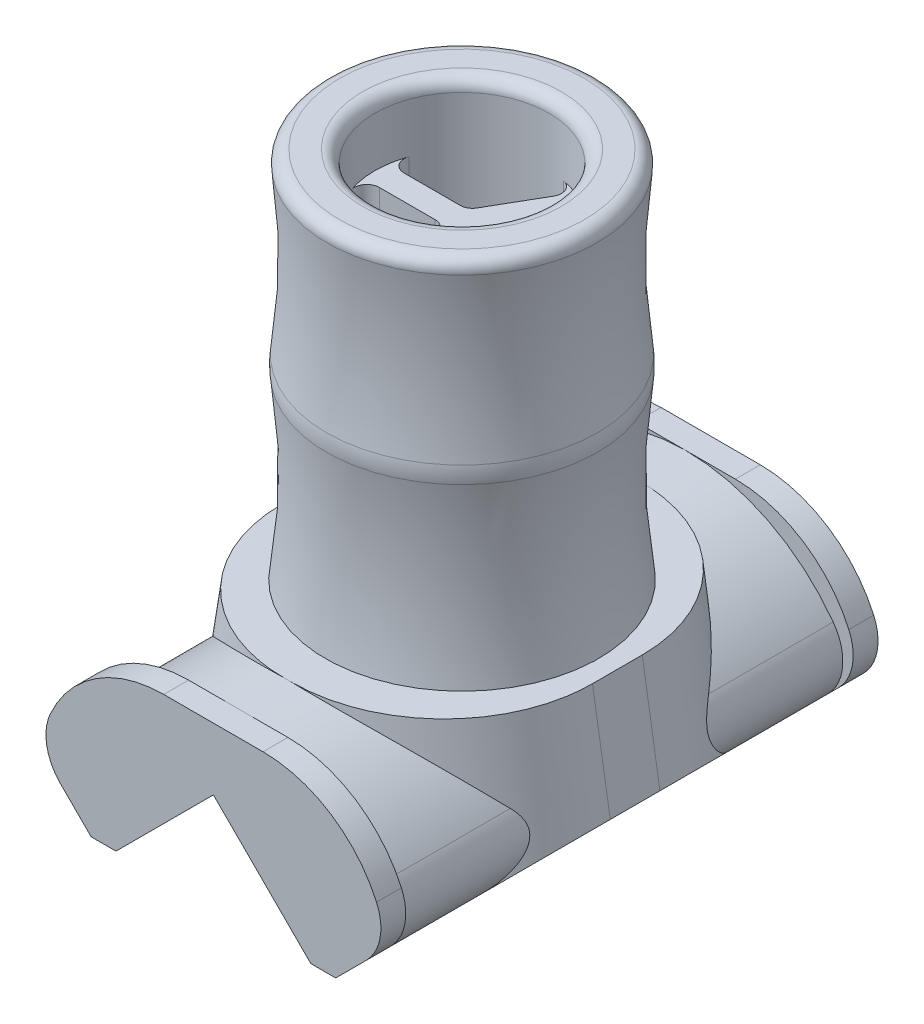
SolidWorks part; units mm, degrees
ref_plane "Front Plane" through (0, 0, 0) normal (0, 0, 1) x (1, 0, 0)
ref_plane "Top Plane" through (0, 0, 0) normal (0, 1, 0) x (1, 0, 0)
ref_plane "Right Plane" through (0, 0, 0) normal (1, 0, 0) x (0, 0, -1)
sketch "Sketch1" plane through (0, 0, 0) normal (0, 0, 1) x (1, 0, 0)
  line L0 (0, 0) -> (17.6777, 17.6777) construction
  line L1 (17.6777, 17.6777) -> (35.3553, 0) construction
  line L2 (35.3553, 0) -> (0, 0) construction
  line L3 (1.7766, 1.7766) -> (5.1777, 22.6777)
  line L4 (5.1777, 22.6777) -> (30.1777, 22.6777)
  line L5 (30.1777, 22.6777) -> (33.5787, 1.7766)
  line L6 (17.6777, 17.6777) -> (17.6777, 22.6777) construction
  line L7 (1.7766, 1.7766) -> (17.6777, 17.6777) construction
  line L8 (17.6777, 17.6777) -> (33.5787, 1.7766) construction
  line L9 (1.7766, 1.7766) -> (4.2951, 1.7766)
  line L10 (33.5787, 1.7766) -> (31.0603, 1.7766)
  line L11 (30.1221, 5.2333) -> (17.6777, 17.6777)
  line L12 (17.6777, 17.6777) -> (5.2333, 5.2333)
  line L13 (17.6777, 0) -> (-4.2005, 21.8781) construction
  line L14 (17.6777, 0) -> (36.9154, 19.2377) construction
  circle A0 centre (17.6777, 0) radius 12.5 construction
  circle A1 centre (17.6777, 0) radius 16 construction
  circle A2 centre (17.6777, 0) radius 13.5 construction
  arc A3 (4.2951, 1.7766) -> (5.2333, 5.2333) centre (17.6777, 0) cw
  arc A4 (31.0603, 1.7766) -> (30.1221, 5.2333) centre (17.6777, 0) ccw
  dimension "D3" = 25
  dimension "D4" = 32
  dimension "D6" = 27
  dimension "D7" = 25
  dimension "D1" = 90
  dimension "D2" = 45
  dimension "D5" = 5
  dimension "D8" = 45
extrude "Boss-Extrude1" add sketch "Sketch1" along normal blind 14 and the other way blind 14
sketch "Sketch2" plane through (0, 22.6777, 0) normal (0, 1, 0) x (1, 0, 0)
  line L0 (5.1777, 0) -> (30.1777, 0) construction
  line L1 (5.1777, 14) -> (5.1777, -14) construction
  line L2 (30.1777, 14) -> (30.1777, -14) construction
  circle A0 centre (17.6777, 0) radius 11
  dimension "D1" = 22
sketch "Sketch3" plane through (0, 0, 0) normal (0, 0, 1) x (1, 0, 0)
  line L0 (17.6777, 22.6777) -> (17.6777, 52.6777) construction
  line L1 (28.6777, 22.6777) -> (6.6777, 22.6777) construction
  line L2 (6.6777, 22.6777) -> (6.6777, 52.6777) construction
  line L3 (6.6777, 52.6777) -> (10.6777, 52.6777)
  line L4 (10.6777, 52.6777) -> (10.6777, 22.6777)
  line L5 (10.6777, 22.6777) -> (6.6777, 22.6777)
  line L7 (5.1777, 22.6777) -> (30.1777, 22.6777) construction
  arc A0 (6.6777, 37.6777) -> (6.6777, 22.6777) centre (-42.7566, 30.1777) cw
  arc A1 (6.6777, 37.6777) -> (6.6777, 52.6777) centre (-42.7566, 45.1777) ccw
  dimension "D3" = 15
  dimension "D4" = 50
  dimension "D5" = 50
  dimension "D1" = 30
  dimension "D2" = 4
revolve "Revolve1" add sketch "Sketch3" angle 360 about L0
fillet "Fillet1" radius 1 2 edges at (17.6777, 52.6777, -7) (17.6777, 52.6777, -11)
sketch "Sketch5" plane through (0, 22.6777, 0) normal (0, 1, 0) x (1, 0, 0)
  line L0 (17.6777, 0) -> (10.6777, 0) construction
  line L1 (17.6777, 1) -> (10.6777, 1)
  line L2 (17.6777, -1) -> (10.6777, -1)
  line L3 (16.8116, 0.5) -> (20.3116, 6.5622)
  line L4 (18.5437, -0.5) -> (22.0437, 5.5622)
  line L5 (18.5437, 0.5) -> (22.0437, -5.5622)
  line L6 (16.8116, -0.5) -> (20.3116, -6.5622)
  circle A0 centre (17.6777, 0) radius 1.004
  circle A1 centre (17.6777, 0) radius 7 construction
  circle A2 centre (17.6777, 0) radius 7
  point P21 (17.6777, 0)
  circle M2 centre (17.6777, 0) radius 7
  dimension "D1" = 1
  dimension "D2" = 1
  dimension "D3" = 3
extrude "Boss-Extrude3" add sketch "Sketch5" along normal blind 25 contours L0 A0 L3 L1 M2 | A0 L0 A2 L2 L6 | A0 L2 L6 L5 L4 M2 | A0 L5 L4 L3 L1 M2 | A0 | A0 L6 L2 | A0 L1 L3 | A0 L4 L5 region at (13.7704, 22.6777, 0.5053) region at (13.7704, 22.6777, -0.5053) region at (16.7475, 22.6777, -0.2941) region at (17.1584, 22.6777, -0.8994) region at (17.1584, 22.6777, 0.8994) region at (19.6313, 22.6777, -3.3838) region at (19.6313, 22.6777, 3.3838) region at (18.7162, 22.6777, 0)
fillet "Fillet2" radius 1 9 edges at (17.1003, 35.1777, -1) (17.1003, 35.1777, 1) (18.8324, 35.1777, 0) (20.2757, 35.1777, 6.5) (22.0078, 35.1777, 5.5) (20.2757, 35.1777, -6.5) (22.0078, 35.1777, -5.5) (10.7495, 35.1777, 1) (10.7495, 35.1777, -1)
sketch "Sketch6" plane through (0, 0, -14) normal (0, 0, -1) x (-1, 0, 0)
  line L0 (-33.5787, 1.7766) -> (-30.1777, 22.6777) construction
  line L1 (-5.1777, 22.6777) -> (-1.7766, 1.7766) construction
  line L2 (-32.1853, 10.3399) -> (-32.0603, 1.7766)
  line L3 (-31.0603, 1.7766) -> (-33.5787, 1.7766) construction
  line L4 (-3.1701, 10.3399) -> (-3.2951, 1.7766)
  line L5 (-1.7766, 1.7766) -> (-4.2951, 1.7766) construction
  line L6 (-30.1777, 22.6777) -> (-5.1777, 22.6777) construction
  line L7 (-32.0603, 1.7766) -> (-31.0603, 1.7766)
  line L8 (-5.2333, 5.2333) -> (-17.6777, 17.6777) construction
  line L9 (-17.6777, 17.6777) -> (-30.1221, 5.2333) construction
  line L10 (-5.2333, 5.2333) -> (-17.6777, 17.6777)
  line L11 (-17.6777, 17.6777) -> (-30.1221, 5.2333)
  line L12 (-4.2951, 1.7766) -> (-3.2951, 1.7766)
  arc A0 (-32.1853, 10.3399) -> (-3.1701, 10.3399) centre (-17.6777, 7.9792) cw
  arc A1 (-4.2951, 1.7766) -> (-5.2333, 5.2333) centre (-17.6777, 0) ccw construction
  arc A2 (-30.1221, 5.2333) -> (-31.0603, 1.7766) centre (-17.6777, 0) ccw construction
  arc A3 (-4.2951, 1.7766) -> (-5.2333, 5.2333) centre (-17.6777, 0) ccw
  arc A4 (-30.1221, 5.2333) -> (-31.0603, 1.7766) centre (-17.6777, 0) ccw
  dimension "D1" = 1
  dimension "D2" = 1
extrude "Boss-Extrude4" add sketch "Sketch6" along normal blind 4
sketch "Sketch7" plane through (0, 0, -18) normal (0, 0, -1) x (-1, 0, 0)
  line L0 (-3.1701, 10.3399) -> (-1.7766, 1.7766) construction
  line L1 (-5.1777, 22.6777) -> (-3.1701, 10.3399) construction
  line L2 (-17.6777, 22.6777) -> (-5.1777, 22.6777) construction
  line L3 (-30.1777, 22.6777) -> (-17.6777, 22.6777) construction
  line L4 (-33.5787, 1.7766) -> (-32.1853, 10.3399) construction
  line L5 (-32.1853, 10.3399) -> (-30.1777, 22.6777) construction
  line L6 (-3.1701, 10.3399) -> (-1.7766, 1.7766)
  line L7 (-5.1777, 22.6777) -> (-3.1701, 10.3399)
  line L8 (-17.6777, 22.6777) -> (-5.1777, 22.6777)
  line L9 (-30.1777, 22.6777) -> (-17.6777, 22.6777)
  line L10 (-33.5787, 1.7766) -> (-32.1853, 10.3399)
  line L11 (-32.1853, 10.3399) -> (-30.1777, 22.6777)
  line L12 (-33.5787, 1.7766) -> (-31.0603, 1.7766)
  line L13 (-1.7766, 1.7766) -> (-4.2951, 1.7766)
  line L14 (-30.1221, 5.2333) -> (-17.6777, 17.6777) construction
  line L15 (-17.6777, 17.6777) -> (-5.2333, 5.2333) construction
  line L16 (-30.1221, 5.2333) -> (-17.6777, 17.6777)
  line L17 (-17.6777, 17.6777) -> (-5.2333, 5.2333)
  arc A0 (-30.1221, 5.2333) -> (-31.0603, 1.7766) centre (-17.6777, 0) ccw construction
  arc A1 (-4.2951, 1.7766) -> (-5.2333, 5.2333) centre (-17.6777, 0) ccw construction
  arc A2 (-30.1221, 5.2333) -> (-31.0603, 1.7766) centre (-17.6777, 0) ccw
  arc A3 (-4.2951, 1.7766) -> (-5.2333, 5.2333) centre (-17.6777, 0) ccw
extrude "Boss-Extrude5" add sketch "Sketch7" along normal blind 2
fillet "Fillet3" radius 5 2 edges at (3.1701, 10.3399, -16) (32.1853, 10.3399, -16)
fillet "Fillet4" radius 10 2 edges at (30.1777, 22.6777, -19) (5.1777, 22.6777, -19)
mirror "Mirror1" about plane through (0, 0, 0) normal (0, 0, 1) of "Fillet3", "Boss-Extrude4", "Fillet4", "Boss-Extrude5"
fillet "Fillet6" radius 12 4 edges at (4.1739, 16.5088, -14) (31.1815, 16.5088, -14) (31.1815, 16.5088, 14) (4.1739, 16.5088, 14)
fillet "Fillet7" radius 5 1 edges at (17.6777, 37.6777, -11)
sketch "Sketch8" plane through (0, 0, 20) normal (0, 0, 1) x (1, 0, 0)
  line L0 (17.6777, 0) -> (0, 17.6777)
  line L1 (17.6777, 0) -> (35.3553, 17.6777)
  line L2 (35.3553, 0) -> (0, 0) construction
  arc A0 (0, 17.6777) -> (35.3553, 17.6777) centre (17.6777, 0) ccw
  dimension "D2" = 25
  dimension "D1" = 45
extrude "Cut-Extrude1" cut sketch "Sketch8" against normal through all
sketch "Sketch10" plane through (0, 0, 20) normal (0, 0, 1) x (1, 0, 0)
  line L0 (7.8388, 9.8388) -> (27.5165, 9.8388)
  line L1 (8.8388, 8.8388) -> (3.7533, 13.9244) construction
  line L2 (31.602, 13.9244) -> (26.5165, 8.8388) construction
  line L3 (7.8388, 9.8388) -> (8.8388, 8.8388)
  line L4 (8.8388, 8.8388) -> (26.5165, 8.8388)
  line L5 (26.5165, 8.8388) -> (27.5165, 9.8388)
  dimension "D1" = 1
extrude "Cut-Extrude2" cut sketch "Sketch10" against normal through all
fillet "Fillet8" radius 4 4 edges at (31.2644, 13.5867, -11.5123) (31.2644, 13.5867, 11.5123) (4.0909, 13.5867, 11.5123) (4.0909, 13.5867, -11.5123)
fillet "Fillet9" radius 4 4 edges at (3.7533, 13.9244, 19) (3.7533, 13.9244, -19) (31.602, 13.9244, -19) (31.602, 13.9244, 19)
